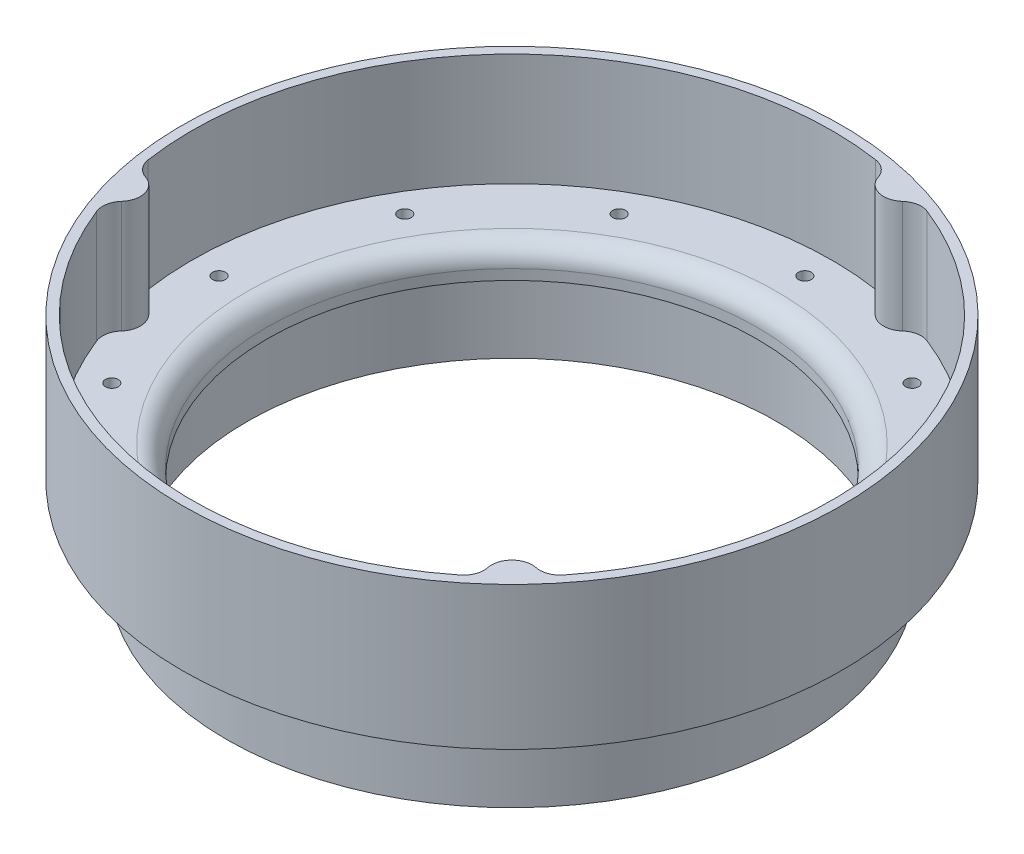
SolidWorks part; units mm, degrees
material "6061-T6 (SS)"
ref_plane "Front Plane" through (0, 0, 0) normal (0, 0, 1) x (1, 0, 0)
ref_plane "Top Plane" through (0, 0, 0) normal (0, 1, 0) x (1, 0, 0)
ref_plane "Right Plane" through (0, 0, 0) normal (1, 0, 0) x (0, 0, -1)
ref_axis "Axis1" through (0, 55, 0) along (0, -1, 0)
sketch "Cross Section" plane through (0, 0, 0) normal (0, 0, 1) x (1, 0, 0)
  line L0 (-38.1, -1.5875) -> (-38.1, -3.175)
  line L1 (-38.1, -3.175) -> (-41.2242, -3.175)
  line L2 (-41.2242, -3.175) -> (-41.2242, -15.875)
  line L4 (0, -15.875) -> (-38.1, -15.875) construction
  line L5 (-44.3992, -15.875) -> (-44.3992, -3.175)
  line L6 (-44.3992, -3.175) -> (-51.2572, -3.175)
  line L7 (-51.2572, -3.175) -> (-51.2572, 19.05)
  line L8 (-51.2572, 19.05) -> (-49.784, 19.05)
  line L9 (-49.784, 19.05) -> (-49.784, 1.5875)
  line L11 (-38.1, 0) -> (0, 0) construction
  line L13 (-44.3992, -15.875) -> (-41.2242, -15.875)
  line L14 (-49.784, 1.5875) -> (-49.784, 3.175) construction
  line L15 (-41.275, 1.5875) -> (-49.784, 1.5875)
  arc A0 (-41.275, 1.5875) -> (-38.1, -1.5875) centre (-41.275, -1.5875) cw
  dimension "D2" = 3.175
  dimension "D1" = 3.1242
  dimension "D3" = 3.175
  dimension "D5" = 6.858
  dimension "D6" = 22.225
  dimension "D9" = 3.175
  dimension "D4" = 1.5875
  dimension "D7" = 38.1
revolve "Main" add sketch "Cross Section" angle 360 about axis through (0, 55, 0) along (0, -1, 0)
sketch "Hole Location" plane through (0, 0, 0) normal (0, 1, 0) x (1, 0, 0)
  line L0 (0, 0) -> (-45.5549, 0) construction
  circle A0 centre (0, 0) radius 45.5549 construction
  dimension "D1" = 91.1098
hole_wizard "#3-48 Tapped Hole1" positions "Sketch1" profile "Sketch2" tap size "#3-48" standard "ANSI Inch" end condition through all
sketch "Sketch1" plane through (0, 1.5875, 0) normal (0, 1, 0) x (1, 0, 0)
  point P0 (-45.5549, 0)
sketch "Sketch2" plane through (-45.5549, 1.5875, 0) normal (1, 0, 0) x (0, 0, 1)
  line L0 (0, 0) -> (0, 17.4625)
  line L1 (0, 17.4625) -> (0.9969, 17.4625)
  line L2 (0.9969, 17.4625) -> (0.9969, 0)
  line L5 (0.9969, 0) -> (0, 0)
  line L11 (0, -6.35) -> (0, 107.95) construction
  dimension "Thru Tap Drill Dia." = 1.9939
  dimension "Thru Tap Drill Depth" = 17.4625
cosmetic thread "Hole Thread1" parameters "D2"=2.5146
pattern_circular "CirPattern1" count 12 over 360 of "#3-48 Tapped Hole1"
sketch "Sketch3" plane through (0, 1.5875, 0) normal (0, 1, 0) x (1, 0, 0)
  line L0 (0, 0) -> (-48.0877, -12.885) construction
  line L1 (0, 0) -> (-45.5549, 0) construction
  circle A0 centre (0, 0) radius 49.784 construction
  circle A1 centre (0, 0) radius 49.784 construction
  circle A2 centre (0, 0) radius 49.784 construction
  arc A3 (-47.095, -9.8692) -> (-45.7201, -15.0005) centre (-48.0877, -12.885) cw
  arc A4 (-45.7201, -15.0005) -> (-46.3057, -18.282) centre (-43.3525, -17.116) ccw
  arc A5 (-47.095, -9.8692) -> (-49.2429, -7.3202) centre (-46.1024, -6.8534) cw
  arc A6 (-46.3057, -18.282) -> (-49.2429, -7.3202) centre (0, 0) cw
  arc A7 (15.0005, 45.7201) -> (9.8692, 47.095) centre (12.885, 48.0877) cw
  arc A8 (9.8692, 47.095) -> (7.3202, 49.2429) centre (6.8534, 46.1024) ccw
  arc A9 (7.3202, 49.2429) -> (18.282, 46.3057) centre (0, 0) cw
  arc A10 (15.0005, 45.7201) -> (18.282, 46.3057) centre (17.116, 43.3525) cw
  arc A11 (32.0945, -35.8509) -> (35.8509, -32.0945) centre (35.2026, -35.2026) cw
  arc A12 (35.8509, -32.0945) -> (38.9855, -30.9609) centre (36.4992, -28.9864) ccw
  arc A13 (38.9855, -30.9609) -> (30.9609, -38.9855) centre (0, 0) cw
  arc A14 (32.0945, -35.8509) -> (30.9609, -38.9855) centre (28.9864, -36.4992) cw
  point P36 (0, 0)
  dimension "D1" = 15
  dimension "D2" = 3.175
  dimension "D3" = 3.175
  dimension "D4" = 3
extrude "Boss-Extrude1" add sketch "Sketch3" along normal up to surface (17.4625 mm away) up to face at (0, 19.05, 51.2572)
equation "\"D1@Hole Location\"=\"TANK DIAMETER@Cryo Tank.Assembly\"+\"GASKET SEAT THICKNESS@Cryo Tank.Assembly\"+\"LINER THICKNESS@Cryo Tank.Assembly\"+\"SHRINK FIT DELTA@Cryo Tank.Assembly\""
equation "\"D1@Cross Section\"=\"LINER THICKNESS@Cryo Tank.Assembly\"-0.002"
equation "\"D3@Cross Section\"=\"ALUMINUM LAP THICKNESS@Cryo Tank.Assembly\""
equation "\"D5@Cross Section\"=2*\"CF THICKNESS@Cryo Tank.Assembly\"+\"NOMEX THICKNESS@Cryo Tank.Assembly\""
equation "\"D7@Cross Section\"=\"TANK DIAMETER@Cryo Tank.Assembly\"/2"
